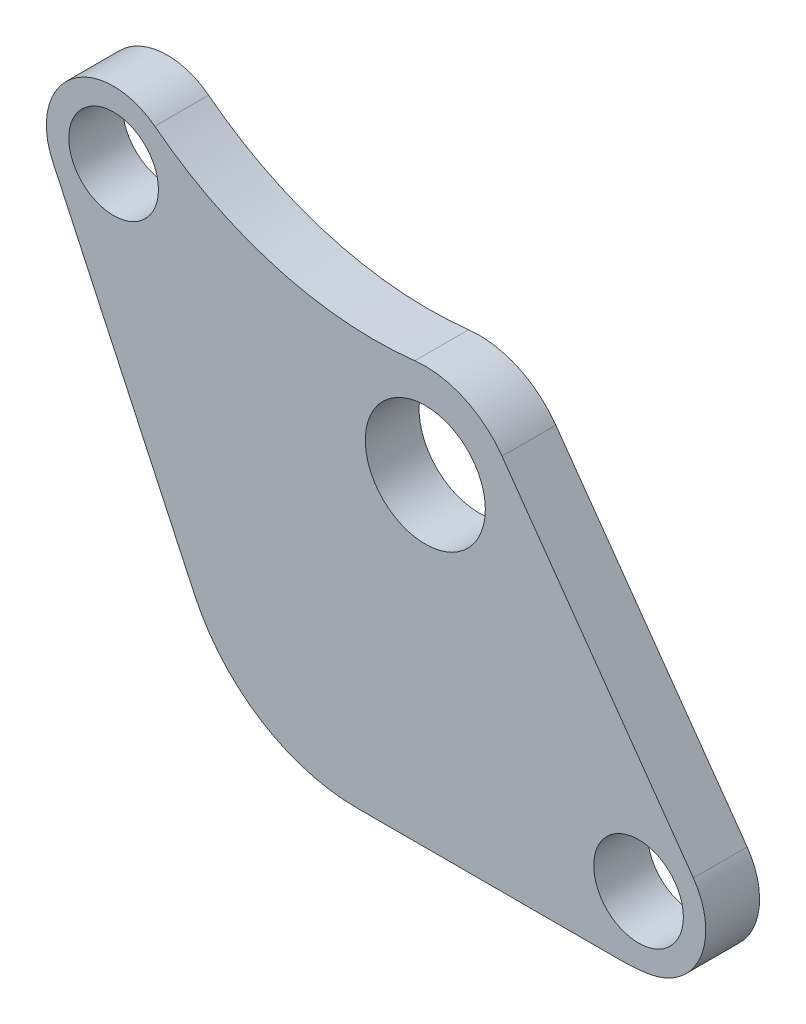
SolidWorks part; units mm, degrees
ref_plane "Front Plane" through (0, 0, 0) normal (0, 0, 1) x (1, 0, 0)
ref_plane "Top Plane" through (0, 0, 0) normal (0, 1, 0) x (1, 0, 0)
ref_plane "Right Plane" through (0, 0, 0) normal (1, 0, 0) x (0, 0, -1)
sketch "Sketch1" plane through (0, 0, 0) normal (0, 0, 1) x (1, 0, 0)
  line L0 (0, 0) -> (12.5, 0) construction
  line L1 (-3.2476, -1.875) -> (0, -3.75) construction
  line L2 (0, -3.75) -> (3.2476, -1.875) construction
  line L3 (3.2476, -1.875) -> (3.2476, 1.875) construction
  line L4 (3.2476, 1.875) -> (0, 3.75) construction
  line L5 (0, 3.75) -> (-3.2476, 1.875) construction
  line L6 (-3.2476, 1.875) -> (-3.2476, -1.875) construction
  line L7 (0, 0) -> (11.8916, -14.1718) construction
  line L9 (-17.3843, 6.3274) -> (0, 0) construction
  line L10 (-16.3063, -18) -> (25.6953, -18) construction
  line L12 (-10.1779, -18) -> (10.9061, -18)
  line L13 (4.2798, 3.0366) -> (14.9499, -12.0018)
  line L14 (-20.783, 4.7426) -> (-10.1779, -18)
  line L15 (0, 0) -> (0, -18) construction
  circle A0 centre (0, 0) radius 12.5 construction
  circle A1 centre (0, 0) radius 3.75 construction
  circle A2 centre (0, 0) radius 5.2476 construction
  circle A3 centre (0, 0) radius 3.2476 construction
  circle A4 centre (-17.3843, 6.3274) radius 2.5
  circle A5 centre (11.8916, -14.1718) radius 2.5
  circle A6 centre (-17.3843, 6.3274) radius 6 construction
  circle A7 centre (11.8916, -14.1718) radius 6 construction
  circle A8 centre (0, 0) radius 3.3476
  circle A9 centre (-17.3843, 6.3274) radius 3.75 construction
  circle A10 centre (11.8916, -14.1718) radius 3.75 construction
  arc A11 (10.9061, -18) -> (12.4828, -17.8749) centre (10.9061, -8) ccw
  arc A12 (-15.0851, 9.2898) -> (-0.5866, 5.2147) centre (-2.8224, 25.0893) ccw
  arc A13 (-15.0851, 9.2898) -> (-20.783, 4.7426) centre (-17.3843, 6.3274) ccw
  arc A14 (-0.5866, 5.2147) -> (4.2798, 3.0366) centre (0, 0) cw
  arc A15 (12.4828, -17.8749) -> (14.9499, -12.0018) centre (11.8916, -14.1718) ccw
  point P30 (-8.3582, -18)
  dimension "D1" = 25
  dimension "D2" = 7.5
  dimension "D3" = 2
  dimension "D4" = 5
  dimension "D7" = 12
  dimension "D9" = 7.5
  dimension "D11" = 20
  dimension "D12" = 10
  dimension "D5" = 50
  dimension "D6" = 20
  dimension "D10" = 18
  dimension "D13" = 65
  dimension "D8" = 0.1
extrude "Boss-Extrude1" add sketch "Sketch1" along normal blind 3
fillet "Fillet1" radius 10 1 edges at (-10.1779, -18, 1.5)
